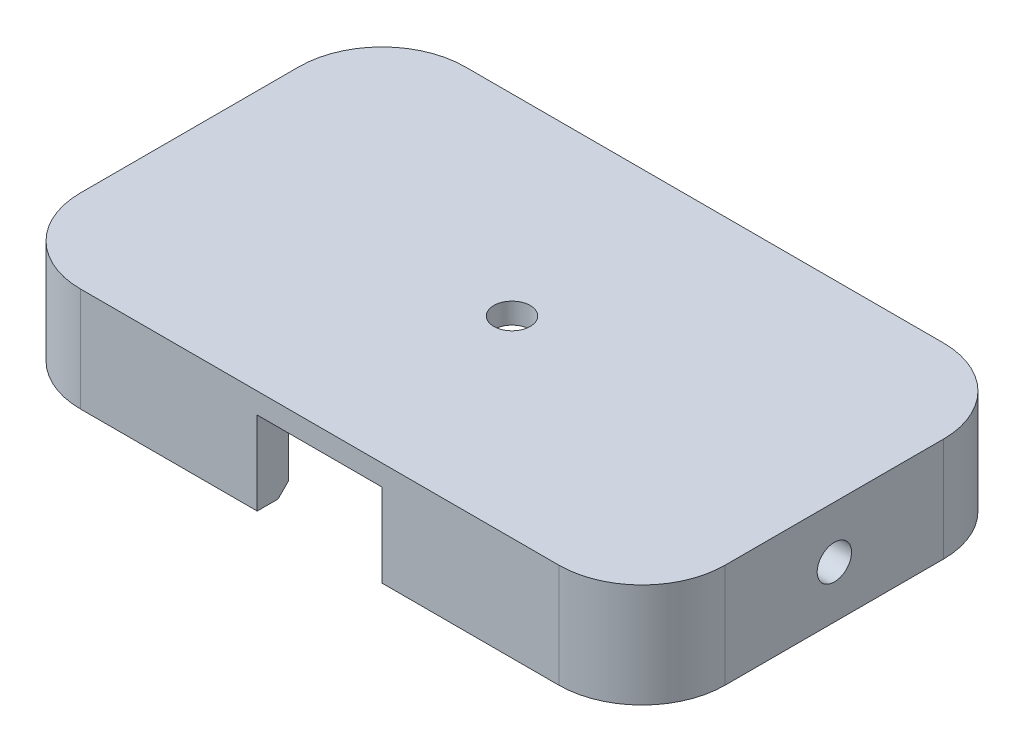
SolidWorks part; units mm, degrees
ref_plane "Front Plane" through (0, 0, 0) normal (0, 0, 1) x (1, 0, 0)
ref_plane "Top Plane" through (0, 0, 0) normal (0, 1, 0) x (1, 0, 0)
ref_plane "Right Plane" through (0, 0, 0) normal (1, 0, 0) x (0, 0, -1)
sketch "Sketch1" plane through (0, 0, 0) normal (0, 1, 0) x (1, 0, 0)
  line L0 (-23, 18.5) -> (23, 18.5)
  line L1 (-23, -15.5) -> (23, -15.5)
  line L2 (-28, -10.5) -> (-28, 10.5)
  line L3 (-23, 15.5) -> (23, 15.5)
  line L4 (28, -10.5) -> (28, 10.5)
  line L5 (-28, -15.5) -> (28, 15.5) construction
  line L6 (-28, 15.5) -> (28, -15.5) construction
  line L7 (31, -10.5) -> (31, 10.5)
  line L8 (-23, -18.5) -> (23, -18.5)
  line L9 (-31, -10.5) -> (-31, 10.5)
  arc A0 (23, 15.5) -> (28, 10.5) centre (23, 10.5) cw
  arc A1 (28, -10.5) -> (23, -15.5) centre (23, -10.5) cw
  arc A2 (-23, -15.5) -> (-28, -10.5) centre (-23, -10.5) cw
  arc A3 (-28, 10.5) -> (-23, 15.5) centre (-23, 10.5) cw
  arc A4 (23, 18.5) -> (31, 10.5) centre (23, 10.5) cw
  arc A5 (31, -10.5) -> (23, -18.5) centre (23, -10.5) cw
  arc A6 (-23, -18.5) -> (-31, -10.5) centre (-23, -10.5) cw
  arc A7 (-31, 10.5) -> (-23, 18.5) centre (-23, 10.5) cw
  point P0 (0, 0)
  dimension "D3" = 5
  dimension "D1" = 56
  dimension "D2" = 31
  dimension "D4" = 3
extrude "Boss-Extrude1" add sketch "Sketch1" against normal blind 10
extrude "Boss-Extrude2" add sketch "Sketch1<2>" against normal blind 2 contours A3 L2 A2 L1 A1 L4 A0 L3 region at (0, 0, 0)
sketch "Sketch1<2>" plane through (0, 0, 0) normal (0, 1, 0) x (1, 0, 0) same geometry as "Sketch1"
hole_wizard "Ø3.3 (3.3) Diameter Hole1" positions "Sketch2" profile "Sketch4" hole size "Ø3.3" standard "ANSI Metric"
sketch "Sketch2" plane through (31, 0, 0) normal (1, 0, 0) x (0, 0, -1)
  line L0 (-10.5, 0) -> (10.5, -10) construction
  point P6 (0, -5)
sketch "Sketch4" plane through (31, -5, 0) normal (0, 1, 0) x (0, 0, -1)
  line L0 (0, 0) -> (0, 10.9914)
  line L1 (0, 10.9914) -> (1.65, 10)
  line L2 (1.65, 10) -> (1.65, 0)
  line L5 (1.65, 0) -> (0, 0)
  line L10 (0, 10.9914) -> (-1.65, 10) construction
  line L11 (0, -6.35) -> (0, 107.95) construction
  dimension "Hole Dia." = 3.3
  dimension "Hole Depth" = 10
  dimension "Drill Angle" = 118
mirror "Mirror1" about plane through (0, 0, 0) normal (1, 0, 0) of "Ø3.3 (3.3) Diameter Hole1"
hole_wizard "Ø3.5 (3.5) Diameter Hole1" positions "Sketch6" profile "Sketch7" hole size "Ø3.5" standard "ANSI Metric" end condition through all
sketch "Sketch6" plane through (0, -2, 0) normal (0, -1, 0) x (-1, 0, 0)
  point P0 (0, 0)
sketch "Sketch7" plane through (0, -2, 0) normal (1, 0, 0) x (0, 0, -1)
  line L0 (0, 0) -> (0, 2)
  line L1 (0, 2) -> (1.75, 2)
  line L2 (1.75, 2) -> (1.75, 0)
  line L5 (1.75, 0) -> (0, 0)
  line L11 (0, -6.35) -> (0, 107.95) construction
  dimension "Thru Hole Dia." = 3.5
  dimension "Thru Hole Depth" = 2
sketch "Sketch8" plane through (0, 0, 18.5) normal (0, 0, 1) x (1, 0, 0)
  line L0 (-23, -10) -> (23, -10) construction
  line L1 (6, -2) -> (-6, -2)
  line L2 (6, -2) -> (6, -10)
  line L3 (6, -10) -> (-6, -10)
  line L4 (-6, -2) -> (-6, -10)
  line L5 (6, -2) -> (-6, -10) construction
  line L6 (6, -10) -> (-6, -2) construction
  line L7 (0, 0) -> (0, -6) construction
  line L8 (-23, 0) -> (23, 0) construction
  point P0 (0, -6)
  dimension "D1" = 12
  dimension "D2" = 8
extrude "Cut-Extrude1" cut sketch "Sketch8" against normal blind 5
chamfer "Chamfer1" distance 1 angle 45 9 edges at (14.5, -10, 15.5) (26.5355, -10, 14.0355) (28, -10, 0) (26.5355, -10, -14.0355) (0, -10, -15.5) (-14.5, -10, 15.5) (-26.5355, -10, -14.0355) (-26.5355, -10, 14.0355) (-28, -10, 0)
